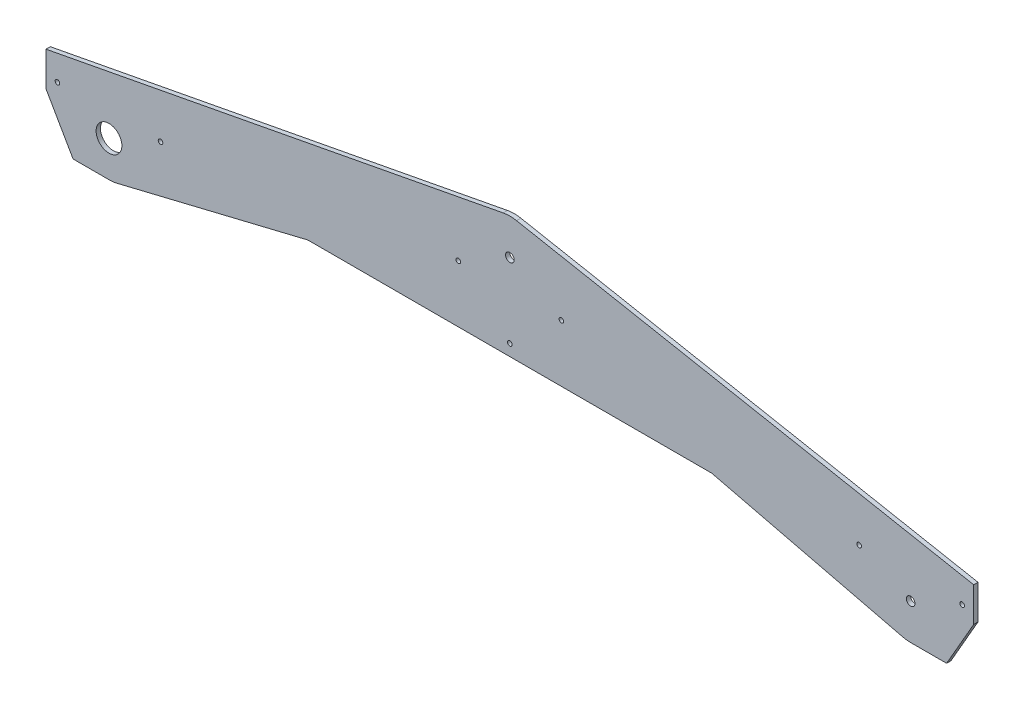
SolidWorks part; units mm, degrees
material "6061-T6 (SS)"
ref_plane "Front Plane" through (0, 0, 0) normal (0, 0, 1) x (1, 0, 0)
ref_plane "Top Plane" through (0, 0, 0) normal (0, 1, 0) x (1, 0, 0)
ref_plane "Right Plane" through (0, 0, 0) normal (1, 0, 0) x (0, 0, -1)
sketch "Model" plane through (0, 0, 0) normal (0, 0, 1) x (1, 0, 0)
  line L0 (379.1498, 1141.1515) -> (590.3783, 1192.3756)
  line L1 (369.7755, 1140.0311) -> (330.0558, 1140.0311)
  line L3 (300.0261, 1230.4756) -> (806.958, 1326.7042)
  line L4 (300.0261, 1230.4756) -> (300.0261, 1192.3756)
  line L5 (300.0261, 1192.3756) -> (330.0558, 1140.0311)
  line L6 (590.3783, 1192.3756) -> (814.3761, 1192.3756)
  line L7 (1249.6023, 1141.1515) -> (1038.3738, 1192.3756)
  line L8 (1258.9766, 1140.0311) -> (1298.6963, 1140.0311)
  line L9 (1328.7261, 1230.4756) -> (821.7942, 1326.7042)
  line L10 (1328.7261, 1230.4756) -> (1328.7261, 1192.3756)
  line L11 (1328.7261, 1192.3756) -> (1298.6963, 1140.0311)
  line L12 (1038.3738, 1192.3756) -> (814.3761, 1192.3756)
  arc A0 (369.7755, 1140.0311) -> (379.1498, 1141.1515) centre (369.7755, 1179.8075) ccw
  arc A1 (821.7942, 1326.7042) -> (806.958, 1326.7042) centre (814.3761, 1287.6256) ccw
  arc A2 (1249.6023, 1141.1515) -> (1258.9766, 1140.0311) centre (1258.9766, 1179.8075) ccw
  circle A4 centre (369.8771, 1179.8075) radius 14.2875
  circle A5 centre (814.3761, 1287.6256) radius 4.7625
  circle A6 centre (1258.875, 1179.8075) radius 4.7625
  circle A7 centre (1201.725, 1205.0756) radius 2.5527
  circle A8 centre (1316.025, 1205.0756) radius 2.5527
  circle A9 centre (757.2271, 1255.8756) radius 2.5527
  circle A10 centre (871.525, 1255.8756) radius 2.5527
  circle A11 centre (814.3761, 1205.0756) radius 2.5527
  circle A12 centre (312.7271, 1205.0756) radius 2.5527
  circle A13 centre (427.0271, 1205.0756) radius 2.5527
extrude "Boss-Extrude1" add sketch "Model" along normal blind 4.7752
ref_axis "Axis1" through (814.3761, 1287.6256, 4.7752) along (0, 0, -1)
ref_axis "Axis2" through (1258.875, 1179.8075, 4.7752) along (0, 0, -1)
ref_axis "Axis3" through (369.8771, 1179.8075, 4.7752) along (0, 0, -1)
